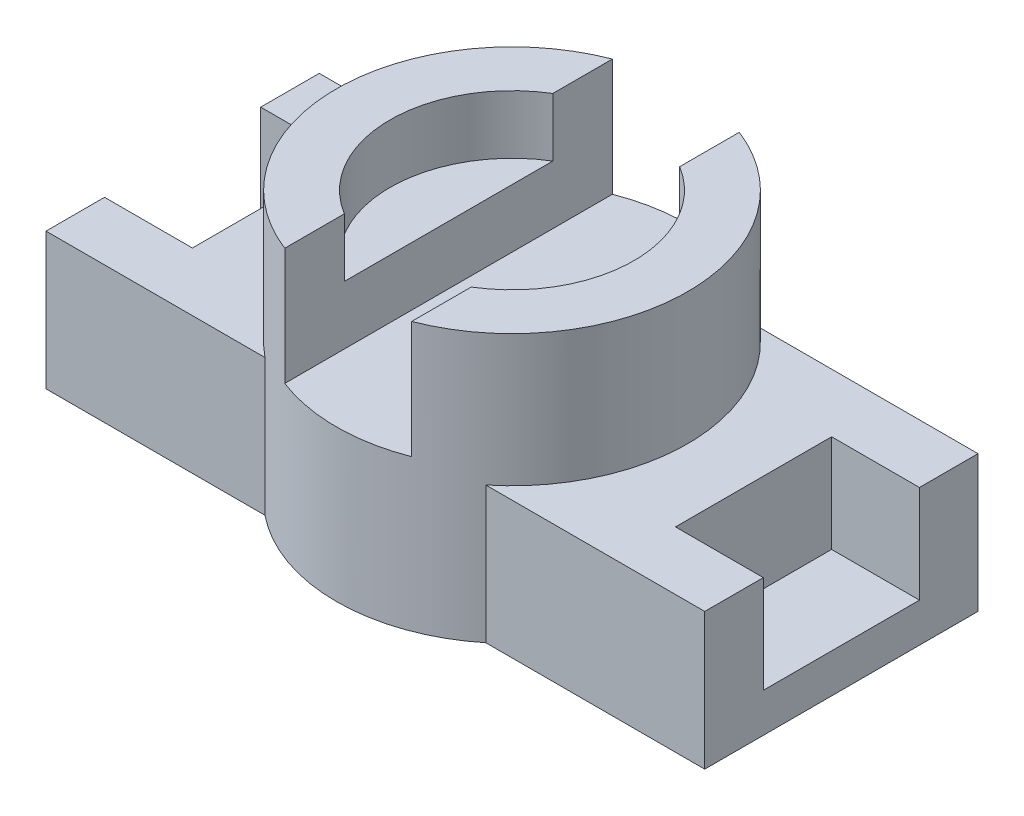
SolidWorks part; units mm, degrees
ref_plane "Front Plane" through (0, 0, 0) normal (0, 0, 1) x (1, 0, 0)
ref_plane "Top Plane" through (0, 0, 0) normal (0, 1, 0) x (1, 0, 0)
ref_plane "Right Plane" through (0, 0, 0) normal (1, 0, 0) x (0, 0, -1)
sketch "Sketch1" plane through (0, 0, 0) normal (0, 1, 0) x (1, 0, 0)
  line L0 (-67.5, -28) -> (67.5, -28)
  line L1 (-67.5, -28) -> (-67.5, 28)
  line L2 (67.5, -28) -> (67.5, 28)
  line L3 (-67.5, 28) -> (67.5, 28)
  line L4 (-67.5, -28) -> (67.5, 28) construction
  line L5 (67.5, -28) -> (-67.5, 28) construction
  line L6 (-13, -42.8235) -> (-13, 42.8235)
  line L7 (-13, -42.8235) -> (13, -42.8235)
  line L8 (-13, 42.8235) -> (13, 42.8235)
  line L9 (13, -42.8235) -> (13, 42.8235)
  line L10 (-13, -42.8235) -> (13, 42.8235) construction
  line L11 (-13, 42.8235) -> (13, -42.8235) construction
  circle A0 centre (0, 0) radius 36
  circle A1 centre (0, 0) radius 25
  point P1 (0, 0)
  dimension "D3" = 50
  dimension "D4" = 72
  dimension "D1" = 135
  dimension "D2" = 56
  dimension "D5" = 26
extrude "Boss-Extrude1" add sketch "Sketch1" along normal blind 28 contours A0 L0 L2 L3 | A0 L3 L1 L0 region at (-49.5117, 0, 0) region at (49.5117, 0, 0)
extrude "Boss-Extrude2" add sketch "Sketch1<3>" along normal blind 55 contours A0
sketch "Sketch1<3>" plane through (0, 0, 0) normal (0, 1, 0) x (1, 0, 0) same geometry as "Sketch1"
extrude "Cut-Extrude1" cut sketch "Sketch1<4>" against normal blind 12 from offset 55 contours A1
sketch "Sketch1<4>" plane through (0, 0, 0) normal (0, 1, 0) x (1, 0, 0) same geometry as "Sketch1"
extrude "Cut-Extrude2" cut sketch "Sketch1<5>" along normal through all from offset 31 contours L9 L8 L6 L7
sketch "Sketch1<5>" plane through (0, 0, 0) normal (0, 1, 0) x (1, 0, 0) same geometry as "Sketch1"
sketch "Sketch2" plane through (0, 28, 0) normal (0, 1, 0) x (1, 0, 0)
  line L0 (-67.5, -28) -> (-67.5, 28) construction
  line L1 (-67.5, 16) -> (-49.5, 16)
  line L2 (-67.5, 16) -> (-67.5, -16)
  line L3 (-67.5, -16) -> (-49.5, -16)
  line L4 (-49.5, 16) -> (-49.5, -16)
  line L5 (0, 0) -> (0, 22.5099) construction
  line L6 (49.5, 16) -> (49.5, -16)
  line L7 (67.5, -16) -> (49.5, -16)
  line L8 (67.5, 16) -> (67.5, -16)
  line L9 (67.5, 16) -> (49.5, 16)
  point P6 (-67.5, 0)
  point P7 (-67.5, 0)
  dimension "D1" = 32
  dimension "D2" = 18
extrude "Cut-Extrude3" cut sketch "Sketch2" against normal blind 20
